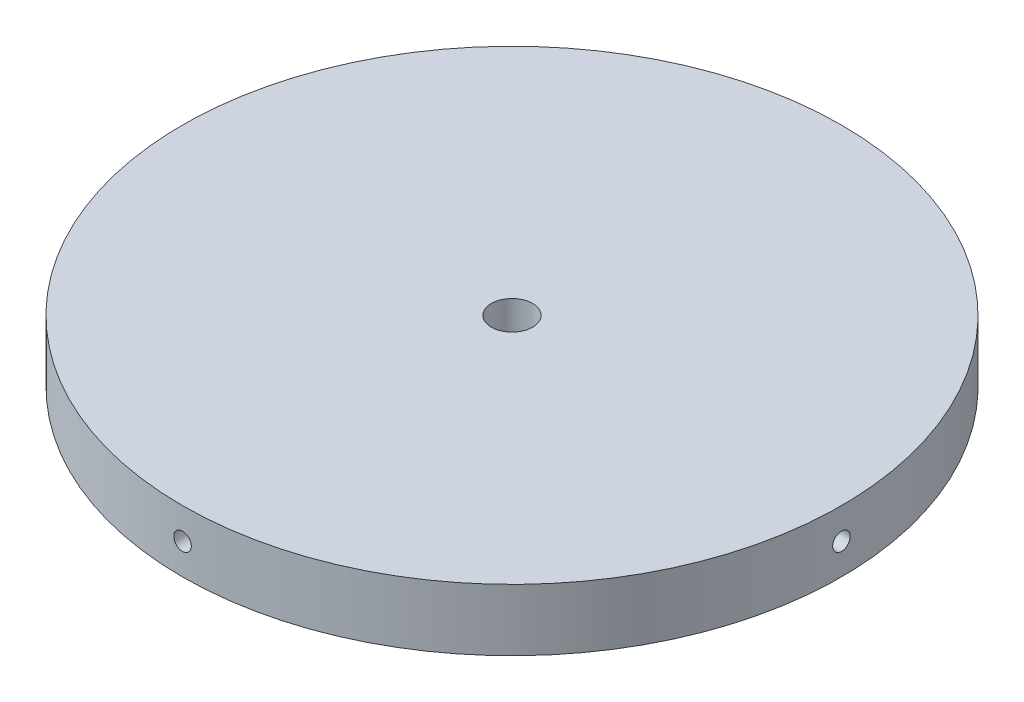
SolidWorks part; units mm, degrees
ref_plane "Front Plane" through (0, 0, 0) normal (0, 0, 1) x (1, 0, 0)
ref_plane "Top Plane" through (0, 0, 0) normal (0, 1, 0) x (1, 0, 0)
ref_plane "Right Plane" through (0, 0, 0) normal (1, 0, 0) x (0, 0, -1)
sketch "Sketch1" plane through (0, 0, 0) normal (0, 1, 0) x (1, 0, 0)
  circle A0 centre (0, 0) radius 50.8
  circle A1 centre (0, 0) radius 3.175
  dimension "D1" = 101.6
  dimension "D2" = 6.35
extrude "Boss-Extrude1" add sketch "Sketch1" along normal mid plane 9.525
ref_plane "Plane1" through (0, 0, 50.8) normal (0, 0, 1) x (1, 0, 0)
sketch "Sketch2" plane through (0, 0, 50.8) normal (0, 0, 1) x (1, 0, 0)
  circle A0 centre (0, 0) radius 1.3526
  dimension "D1" = 2.7051
extrude "Cut-Extrude1" cut sketch "Sketch2" against normal blind 12.7
sketch "Sketch3" plane through (0, 0, 0) normal (0, 0, 1) x (1, 0, 0)
  line L0 (0, 4.7625) -> (0, -4.7625)
  line L1 (50.8, 4.7625) -> (-50.8, 4.7625) construction
  line L2 (-50.8, -4.7625) -> (50.8, -4.7625) construction
pattern_circular "CirPattern1" count 4 over 360 about axis through (0, 4.7625, 0) along (0, -1, 0) of "Cut-Extrude1"
